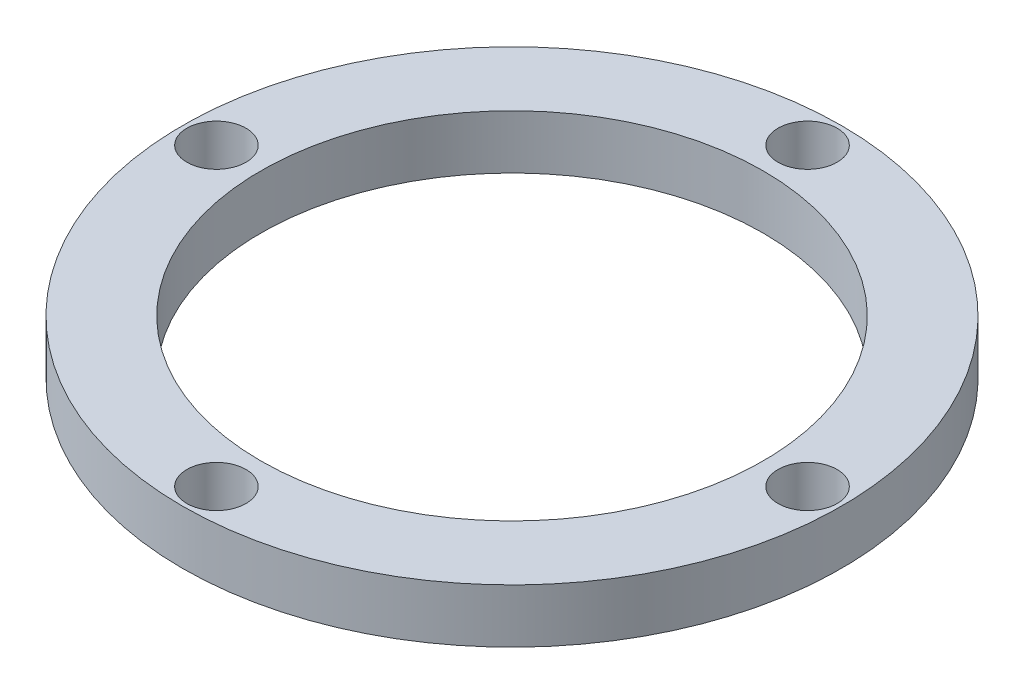
SolidWorks part; units mm, degrees
ref_plane "Front" through (0, 0, 0) normal (0, 0, 1) x (1, 0, 0)
ref_plane "Top" through (0, 0, 0) normal (0, 1, 0) x (1, 0, 0)
ref_plane "Right" through (0, 0, 0) normal (1, 0, 0) x (0, 0, -1)
sketch "Sketch1" plane through (0, 0, 0) normal (0, 1, 0) x (1, 0, 0)
  circle A0 centre (0, 0) radius 17
  circle A1 centre (0, 0) radius 22.3005
extrude "Boss-Extrude1" add sketch "Sketch1" along normal blind 3.65
sketch "Sketch2" plane through (0, 3.65, 0) normal (0, 1, 0) x (1, 0, 0)
  line L0 (0, 0) -> (0, 20)
  circle A0 centre (0, 20) radius 2
  circle A1 centre (20, 0) radius 2
  circle A2 centre (0, -20) radius 2
  circle A3 centre (-20, 0) radius 2
  point P13 (0, 0)
  dimension "D2" = 4
  dimension "D1" = 20
extrude "Cut-Extrude1" cut sketch "Sketch2" against normal through all contours A0 | A1 | A2 | A3 region at (1.3742, 3.65, -18.6258) region at (20, 3.65, 0) region at (0, 3.65, 20)
